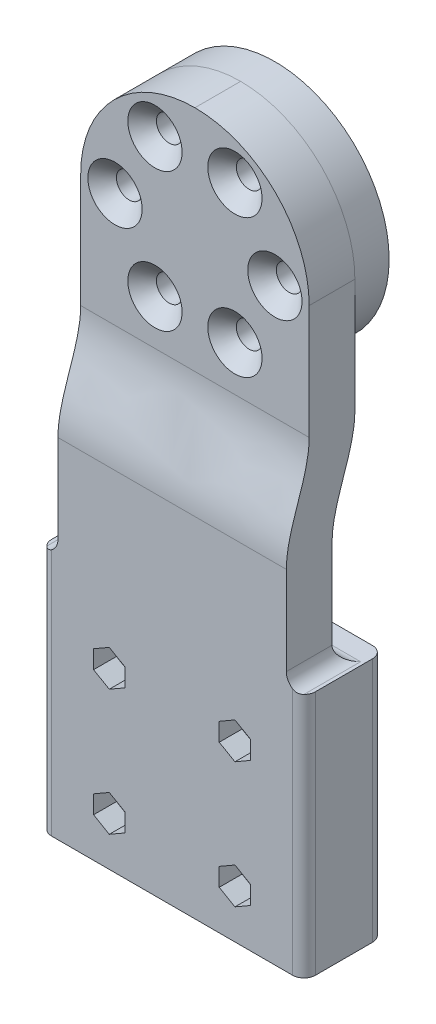
SolidWorks part; units mm, degrees
other "Markup1"
sketch "Sketch13" plane through (20, -53, 11) normal (0.0614, -0.6805, 0.7302) x (0.9699, -0.1321, -0.2046)
ref_plane "Front Plane" through (0, 0, 0) normal (0, 0, 1) x (1, 0, 0)
ref_plane "Top Plane" through (0, 0, 0) normal (0, 1, 0) x (1, 0, 0)
ref_plane "Right Plane" through (0, 0, 0) normal (1, 0, 0) x (0, 0, -1)
sketch "Sketch7" plane through (0, 0, 0) normal (0, 0, 1) x (1, 0, 0)
  line L1 (-20, 20) -> (20, 20)
  line L2 (-20, 20) -> (-20, -20)
  line L3 (-20, -20) -> (20, -20)
  line L4 (20, 20) -> (20, -20)
  line L5 (-20, 20) -> (20, -20) construction
  line L6 (-20, -20) -> (20, 20) construction
  point P0 (0, 0)
extrude "Boss-Extrude1" add sketch "Sketch7" along normal blind 14
ref_plane "Plane2" through (0, -22.1603, 5.9378) normal (0, -0.9659, 0.2588) x (1, 0, 0)
sketch "Sketch8" plane through (0, -20, 2.0782) normal (0, -1, 0) x (1, 0, 0)
  line L0 (20, 11.9218) -> (20, -2.0782) construction
  line L1 (-20, 11.9218) -> (20, 11.9218)
  line L2 (-20, 11.9218) -> (-20, 3.9218)
  line L3 (-20, 3.9218) -> (20, 3.9218)
  line L4 (20, 11.9218) -> (20, 3.9218)
  line L5 (0, 3.9218) -> (0, 11.9218) construction
  line L6 (-20, 7.9218) -> (20, 7.9218) construction
  line L7 (-20, -2.0782) -> (20, -2.0782) construction
  point P764 (0, 7.9218)
  dimension "D1" = 6
ref_plane "Plane4" through (0, -38, 0) normal (0, -1, 0) x (-1, 0, 0)
sketch "Sketch19" plane through (0, -38, 0) normal (0, -1, 0) x (-1, 0, 0)
  line L5 (20, -10) -> (-20, -10) construction
  line L6 (20, -18) -> (-20, -18)
  line L10 (20, -18) -> (20, -10)
  line L11 (20, -10) -> (-20, -10)
  line L12 (-20, -18) -> (-20, -10)
  line L13 (20, -18) -> (-20, -10) construction
  line L14 (20, -10) -> (-20, -18) construction
  line L16 (20, -14) -> (20, 0) construction
  point P0 (0, -14)
  dimension "D1" = 40
  dimension "D2" = 8
  dimension "D3" = 4
loft "Loft1" add profiles "Sketch19", "Sketch8<3>" start constraint normal to profile start tangent length 1 end constraint normal to profile end tangent length 1 connector at (-20, -38, 18) connector at (-20, -20, 14)
sketch "Sketch8<3>" plane through (0, -20, 2.0782) normal (0, -1, 0) x (1, 0, 0) same geometry as "Sketch8"
sketch "Sketch16" plane through (0, 0, 0) normal (0, 0, -1) x (-1, 0, 0)
  line L1 (24.5131, 32.6211) -> (-24.5131, 32.6211)
  line L2 (24.5131, 32.6211) -> (24.5131, -32.6211)
  line L3 (24.5131, -32.6211) -> (-24.5131, -32.6211)
  line L4 (-24.5131, 32.6211) -> (-24.5131, -32.6211)
  line L5 (24.5131, 32.6211) -> (-24.5131, -32.6211) construction
  line L6 (24.5131, -32.6211) -> (-24.5131, 32.6211) construction
  circle A0 centre (0, 0) radius 20
extrude "Cut-Extrude3" cut sketch "Sketch16" against normal blind 6
ref_plane "Plane3" [suppressed] through (0, -56, 0) normal (0, -1, 0) x (-1, 0, 0)
sketch "Sketch17" plane through (0, -38, 0) normal (0, -1, 0) x (-1, 0, 0)
  line L1 (20, -18) -> (-20, -18)
  line L2 (20, -18) -> (20, -10)
  line L3 (20, -10) -> (-20, -10)
  line L4 (-20, -18) -> (-20, -10)
  line L5 (20, -18) -> (-20, -10) construction
  line L6 (20, -10) -> (-20, -18) construction
  line L7 (-20, -18) -> (20, -18) construction
  line L11 (-20, -6) -> (-20, -10) construction
  line L12 (20, -14) -> (20, -6) construction
  point P4 (0, -14)
  dimension "D1" = 8
extrude "Boss-Extrude5" add sketch "Sketch17" along normal blind 18
sketch "Sketch10" plane through (0, 0, 14) normal (0, 0, 1) x (1, 0, 0)
  circle A0 centre (-7.0001, 12.1244) radius 2.25
  circle A1 centre (6.9999, 12.1244) radius 2.25
  circle A2 centre (13.9999, 0.0001) radius 2.25
  circle A3 centre (6.9999, -12.1243) radius 2.25
  circle A4 centre (-7.0001, -12.1243) radius 2.25
  circle A5 centre (-14.0001, 0.0001) radius 2.25
  point P0 (0, 0)
  point P1 (0.0025, 0.0011)
  dimension "D4" = 4.5
extrude "Cut-Extrude1" cut sketch "Sketch10" against normal blind 25
sketch "Sketch11" plane through (0, -56, -3.473) normal (0, 1, 0) x (1, 0, 0)
  line L0 (20, -21.473) -> (-20, -21.473) construction
  line L5 (23.1, -7.473) -> (-23.1, -7.473)
  line L6 (23.1, -7.473) -> (23.1, -21.473)
  line L7 (23.1, -21.473) -> (-23.1, -21.473)
  line L8 (-23.1, -7.473) -> (-23.1, -21.473)
  line L9 (23.1, -7.473) -> (-23.1, -21.473) construction
  line L10 (23.1, -21.473) -> (-23.1, -7.473) construction
  line L16 (20, -13.473) -> (20, -21.473) construction
  point P0 (0, -14.473)
  dimension "D1" = 46.2
  dimension "D2" = 3.1
  dimension "D3" = 14
chamfer "Chamfer1" distance 2.5 angle 45 6 edges at (-4.7501, 12.1244, 14) (-11.7501, 0.0001, 14) (-4.7501, -12.1243, 14) (9.2499, 12.1244, 14) (16.2499, 0.0001, 14) (9.2499, -12.1243, 14)
fillet "Fillet3" radius 20 2 edges at (20, 20, 10) (-20, 20, 10)
extrude "Boss-Extrude6" add sketch "Sketch11" against normal blind 43
fillet "Fillet9" radius 2.5 3 edges at (0, -56, 10) (-20, -56, 14) (20, -56, 14)
ref_plane "Plane5" through (0, -99, 0) normal (0, -1, 0) x (-1, 0, 0)
sketch "Sketch20" plane through (0, -99, 0) normal (0, -1, 0) x (1, 0, 0)
  line L0 (0, 4) -> (0, 18) construction
  line L1 (20.3, 8.8) -> (-20.3, 8.8)
  line L2 (20.3, 8.8) -> (20.3, 13.2)
  line L3 (20.3, 13.2) -> (-20.3, 13.2)
  line L4 (-20.3, 8.8) -> (-20.3, 13.2)
  line L5 (20.3, 8.8) -> (-20.3, 13.2) construction
  line L6 (20.3, 13.2) -> (-20.3, 8.8) construction
  line L7 (23.1, 4) -> (-23.1, 4) construction
  line L8 (-23.1, 18) -> (23.1, 18) construction
  line L9 (-23.1, 4) -> (-23.1, 18) construction
  point P0 (0, 11)
  dimension "D1" = 4.4
  dimension "D2" = 40.6
  dimension "D3" = 23.1
  dimension "D4" = 7
extrude "Cut-Extrude4" cut sketch "Sketch20" against normal blind 40
sketch "Sketch22" plane through (0, 0, 0) normal (0, 0, 1) x (1, 0, 0)
  line L0 (-7.7, -99) -> (7.7, -99) construction
  line L1 (20, -99) -> (-20, -99)
  line L2 (20, -99) -> (20, -59)
  line L3 (20, -59) -> (-20, -59)
  line L4 (-20, -99) -> (-20, -59)
  line L5 (20, -99) -> (-20, -59) construction
  line L6 (20, -59) -> (-20, -99) construction
  line L9 (23.1, -99) -> (23.1, -56) construction
  circle A0 centre (-11, -68.5) radius 1.7
  circle A1 centre (11, -68.5) radius 1.7
  circle A2 centre (11, -90.5) radius 1.7
  circle A3 centre (-11, -90.5) radius 1.7
  point P0 (0, -79)
  dimension "D4" = 3.4
  dimension "D1" = 40
  dimension "D2" = 40
  dimension "D3" = 23.1
  dimension "D5" = 9.5
  dimension "D6" = 8.5
  dimension "D7" = 9
  dimension "D8" = 9
  dimension "D9" = 8.5
  dimension "D10" = 9
  dimension "D11" = 22
extrude "Cut-Extrude5" cut sketch "Sketch22" along normal blind 30 contours A1 | A2 | A3 | A0 region at (-11, -68.5, 0) region at (11, -68.5, 0) region at (11, -90.5, 0) region at (-11, -90.5, 0)
fillet "Fillet11" radius 2 4 edges at (-23.1, -77.5, 18) (-23.1, -77.5, 4) (23.1, -77.5, 18) (23.1, -77.5, 4)
ref_plane "Plane6" through (0, 0, 18) normal (0, 0, 1) x (1, 0, 0)
sketch "Sketch23" plane through (0, 0, 18) normal (0, 0, 1) x (1, 0, 0)
  line L0 (-13.75, -66.9123) -> (-8.25, -70.0877) construction
  line L1 (-11, -65.3246) -> (-13.75, -66.9123)
  line L2 (-13.75, -66.9123) -> (-13.75, -70.0877)
  line L3 (-13.75, -70.0877) -> (-11, -71.6754)
  line L4 (-11, -71.6754) -> (-8.25, -70.0877)
  line L5 (-8.25, -70.0877) -> (-8.25, -66.9123)
  line L6 (-8.25, -66.9123) -> (-11, -65.3246)
  line L7 (-11, -65.3246) -> (-11, -71.6754) construction
  line L8 (11, -65.3246) -> (11, -71.6754) construction
  line L9 (11, -65.3246) -> (8.25, -66.9123)
  line L10 (8.25, -66.9123) -> (8.25, -70.0877)
  line L11 (8.25, -70.0877) -> (11, -71.6754)
  line L12 (11, -71.6754) -> (13.75, -70.0877)
  line L13 (13.75, -70.0877) -> (13.75, -66.9123)
  line L14 (13.75, -66.9123) -> (11, -65.3246)
  line L15 (11, -87.3246) -> (8.25, -88.9123)
  line L16 (8.25, -88.9123) -> (8.25, -92.0877)
  line L17 (8.25, -92.0877) -> (11, -93.6754)
  line L18 (11, -93.6754) -> (13.75, -92.0877)
  line L19 (13.75, -92.0877) -> (13.75, -88.9123)
  line L20 (13.75, -88.9123) -> (11, -87.3246)
  line L21 (-11, -87.3246) -> (-13.75, -88.9123)
  line L22 (-13.75, -88.9123) -> (-13.75, -92.0877)
  line L23 (-13.75, -92.0877) -> (-11, -93.6754)
  line L24 (-11, -93.6754) -> (-8.25, -92.0877)
  line L25 (-8.25, -92.0877) -> (-8.25, -88.9123)
  line L26 (-8.25, -88.9123) -> (-11, -87.3246)
  line L27 (11, -87.3246) -> (11, -94.13) construction
  line L28 (-11, -87.3246) -> (-11, -93.6754) construction
  circle A0 centre (-11, -68.5) radius 2.75 construction
  circle A1 centre (11, -68.5) radius 2.75 construction
  circle A2 centre (11, -90.5) radius 2.75 construction
  circle A3 centre (-11, -90.5) radius 2.75 construction
  point P28 (-13.75, -90.5)
  dimension "D1" = 5.5
  dimension "D2" = 60
  dimension "D3" = 5.5
  dimension "D4" = 5.5
  dimension "D5" = 5.5
extrude "Cut-Extrude6" cut sketch "Sketch23" against normal blind 4
ref_plane "Plane7" through (0, 0, 4) normal (0, 0, -1) x (-1, 0, 0)
sketch "Sketch24" plane through (0, 0, 4) normal (0, 0, -1) x (-1, 0, 0)
  circle A0 centre (-11, -68.5) radius 3
  circle A1 centre (11, -68.5) radius 3
  circle A2 centre (11, -90.5) radius 3
  circle A3 centre (-11, -90.5) radius 3
  dimension "D1" = 6
  dimension "D2" = 6
  dimension "D3" = 6
  dimension "D4" = 6
extrude "Cut-Extrude7" cut sketch "Sketch24" against normal blind 3 contours A1 | A2 | A3 | A0
